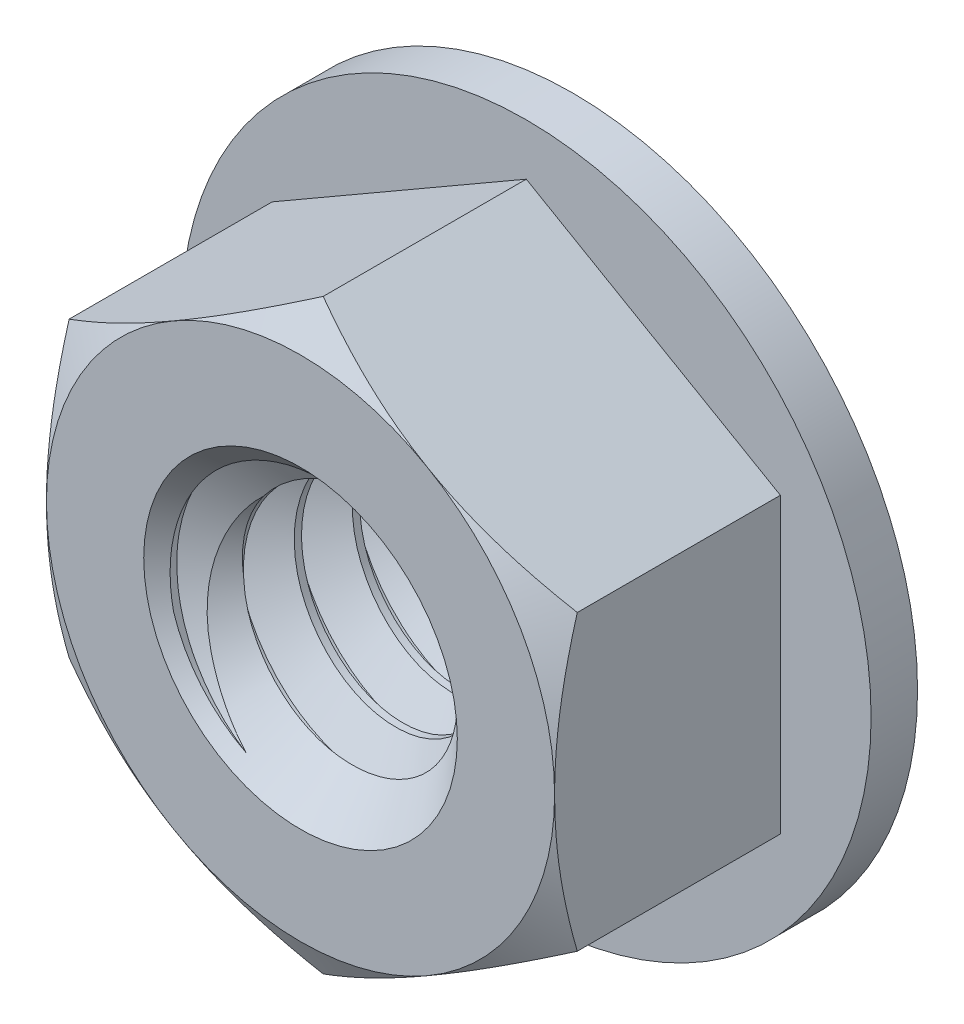
SolidWorks part; units mm, degrees
ref_plane "Front Plane" through (0, 0, 0) normal (0, 0, 1) x (1, 0, 0)
ref_plane "Top Plane" through (0, 0, 0) normal (0, 1, 0) x (1, 0, 0)
ref_plane "Right Plane" through (0, 0, 0) normal (1, 0, 0) x (0, 0, -1)
sketch "Sketch1" plane through (0, 0, 0) normal (0, 0, 1) x (1, 0, 0)
  line L1 (0, 6.4158) -> (-5.5563, 3.2079)
  line L2 (-5.5563, 3.2079) -> (-5.5563, -3.2079)
  line L3 (-5.5563, -3.2079) -> (0, -6.4158)
  line L4 (0, -6.4158) -> (5.5562, -3.2079)
  line L5 (5.5562, -3.2079) -> (5.5563, 3.2079)
  line L6 (5.5563, 3.2079) -> (0, 6.4158)
  circle A0 centre (0, 0) radius 5.5563 construction
  dimension "Hex" = 11.1125
extrude "Extrude1" add sketch "Sketch1" against normal blind 5.9531
sketch "Sketch13" plane through (0, 0, -5.9531) normal (0, 0, -1) x (-1, 0, 0)
  circle A0 centre (0, 0) radius 7.5406
  dimension "Flange od" = 15.0812
extrude "Extrude3" add sketch "Sketch13" against normal blind 1.016
sketch "Sketch2" plane through (0, 0, 0) normal (0, 0, 1) x (1, 0, 0)
  circle A0 centre (0, 0) radius 5.5563 construction
  circle A1 centre (0, 0) radius 5.5563
extrude "Cut-Extrude1" cut sketch "Sketch2" against normal through all draft 60 flip side to cut
sketch "Sketch4" plane through (0, 0, 0) normal (0, 0, 1) x (1, 0, 0)
  circle A0 centre (0, 0) radius 3.175
  dimension "Thread Dia" = 6.35
extrude "Cut-Extrude3" cut sketch "Sketch4" against normal through all
sketch "Sketch7" plane through (0, 0, 0) normal (0, 0, 1) x (1, 0, 0)
  circle A4 centre (0, 0) radius 3.429
  circle A5 centre (0, 0) radius 3.429
  dimension "D1" = 0.254
sketch "Sketch8" plane through (0, 0, -5.9531) normal (0, 0, -1) x (-1, 0, 0)
  circle A1 centre (0, 0) radius 3.429
  circle A2 centre (0, 0) radius 3.429 construction
sketch "Sketch5" plane through (0, 0, 0) normal (0, 0, 1) x (1, 0, 0)
  circle A0 centre (0, 0) radius 3.175 construction
  circle A1 centre (0, 0) radius 3.175
curve "Helix/Spiral1" pitch 1.27 height 7.2231 turns 5.6875 parameters "pitch"=1.27
sketch "Sketch9" plane through (0, 0, 0) normal (1, 0, 0) x (0, 0, -1)
  line L0 (-0.635, 3.175) -> (-0.4762, 3.175)
  line L1 (-0.4762, 3.175) -> (0, 2.3501)
  line L2 (-0.635, 3.175) -> (-1.1112, 2.3501)
  line L3 (-1.1112, 2.3501) -> (0, 2.3501)
  line L4 (-0.5556, 3.175) -> (-0.5556, 2.3501) construction
  line L5 (-0.8731, 2.7626) -> (-0.2381, 2.7626) construction
  line L7 (0, 2.3501) -> (0, 3.175) construction
  line L8 (0, 3.175) -> (0, -3.175) construction
  dimension "D1" = 0.1588
  dimension "D2" = 0.635
  dimension "D3" = 60
sketch "Sketch12" plane through (0, 0, 0) normal (0, 0, 1) x (1, 0, 0)
  circle A0 centre (0, 0) radius 2.3501
  circle A1 centre (0, 0) radius 3.175 construction
  circle A2 centre (0, 0) radius 3.175
extrude "Extrude2" add sketch "Sketch12" against normal up to surface (5.9531 mm away) up to face at (3.175, 0, -5.9531)
sweep "Cut-Sweep1" cut profiles "Sketch9" path "Helix/Spiral1"
extrude "Cut-Extrude6" cut sketch "Sketch7" against normal through all draft 45
extrude "Cut-Extrude7" cut sketch "Sketch8" against normal through all draft 45
equation "\"D2@Sketch9\" = \"pitch@Helix/Spiral1\"*.5"
equation "\"D3@Helix/Spiral1\" = \"pitch@Helix/Spiral1\"+\"Height@Extrude1\""
equation "\"D1@Sketch9\" = \"pitch@Helix/Spiral1\"*.125"
